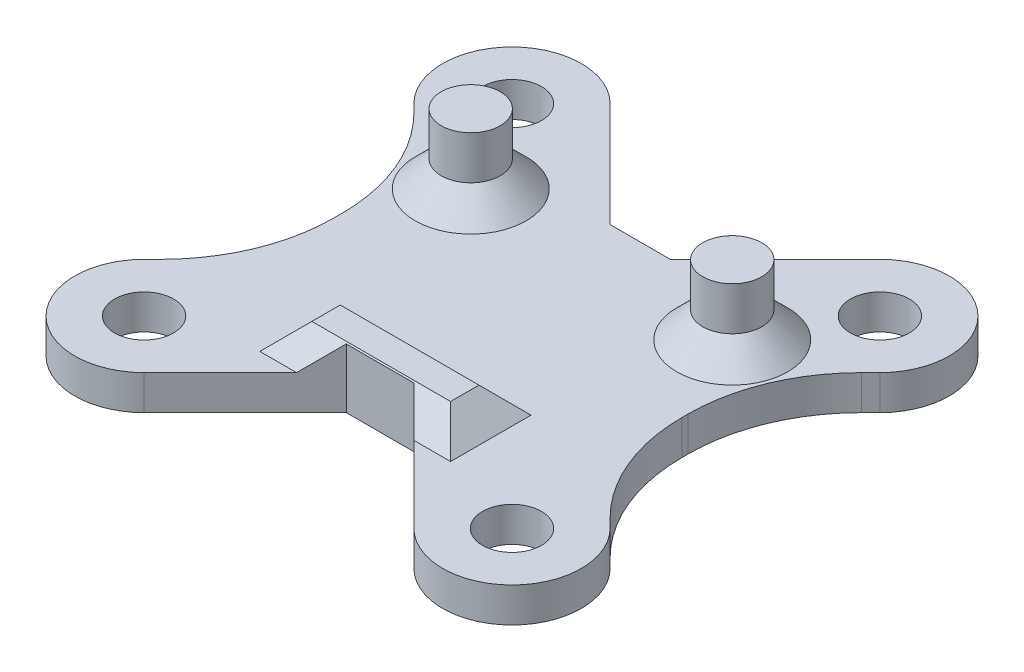
SolidWorks part; units mm, degrees
ref_plane "Front Plane" through (0, 0, 0) normal (0, 0, 1) x (1, 0, 0)
ref_plane "Top Plane" through (0, 0, 0) normal (0, 1, 0) x (1, 0, 0)
ref_plane "Right Plane" through (0, 0, 0) normal (1, 0, 0) x (0, 0, -1)
sketch "Sketch2" plane through (0, 0, 0) normal (0, 1, 0) x (1, 0, 0)
  line L0 (-10.6066, 10.6066) -> (10.6066, -10.6066) construction
  line L1 (-10.6066, -10.6066) -> (10.6066, 10.6066) construction
  line L2 (-13.435, 7.7782) -> (-10.0286, 4.3718)
  line L3 (9.9714, -4.3145) -> (9.9714, 4.3145)
  line L4 (-7.7782, -13.435) -> (-1.9497, -7.6066)
  line L5 (-7.7782, 13.435) -> (-1.7365, 7.3934)
  line L6 (-13.435, -7.7782) -> (-10.0286, -4.3718)
  line L7 (1.7365, 7.3934) -> (7.7782, 13.435)
  line L8 (1.9497, -7.6066) -> (7.7782, -13.435)
  line L9 (1.7365, 7.3934) -> (-1.7365, 7.3934)
  line L10 (9.9714, 4.3145) -> (13.435, 7.7782)
  line L11 (9.9714, -4.3145) -> (13.435, -7.7782)
  line L12 (1.9497, -7.6066) -> (-1.9497, -7.6066)
  line L13 (-10.0286, -4.3718) -> (-10.0286, 4.3718)
  circle A0 centre (-10.6066, -10.6066) radius 1.7
  circle A1 centre (10.6066, -10.6066) radius 1.7
  circle A2 centre (10.6066, 10.6066) radius 1.7
  circle A3 centre (-10.6066, 10.6066) radius 1.7
  arc A4 (-7.7782, 13.435) -> (-13.435, 7.7782) centre (-10.6066, 10.6066) ccw
  arc A5 (13.435, 7.7782) -> (7.7782, 13.435) centre (10.6066, 10.6066) ccw
  arc A6 (7.7782, -13.435) -> (13.435, -7.7782) centre (10.6066, -10.6066) ccw
  arc A7 (-13.435, -7.7782) -> (-7.7782, -13.435) centre (-10.6066, -10.6066) ccw
  point P24 (0, 0)
extrude "Boss-Extrude1" add sketch "Sketch2" along normal blind 2 contours L9 L5 A4 L2 L13 L6 A7 L4 L12 L8 A6 L11 L3 L10 A5 L7
sketch "Sketch3" plane through (0, 2, 0) normal (0, 1, 0) x (1, 0, 0)
  point P0 (-10.6066, -10.6066)
  point P2 (10.6066, -10.6066)
  point P4 (10.6066, 10.6066)
  point P6 (-10.6066, 10.6066)
hole_wizard "M3 Clearance Hole1" positions "Sketch3" profile "Sketch4" hole size "M3" standard "ISO" end condition through all
sketch "Sketch4" plane through (-10.6066, 2, 10.6066) normal (1, 0, 0) x (0, 0, 1)
  line L0 (0, 0) -> (0, 2)
  line L1 (0, 2) -> (1.7, 2)
  line L2 (1.7, 2) -> (1.7, 0)
  line L5 (1.7, 0) -> (0, 0)
  line L11 (0, -6.35) -> (0, 107.95) construction
  dimension "Thru Hole Dia." = 3.4
  dimension "Thru Hole Depth" = 2
sketch "Sketch5" plane through (0, 2, 0) normal (0, 1, 0) x (1, 0, 0)
  line L0 (-7.54, 5.16) -> (7.54, 5.16) construction
  line L1 (-10.32, -7.54) -> (10.32, -7.54)
  line L2 (-10.32, -7.54) -> (-10.32, 7.54)
  line L3 (-10.32, 7.54) -> (10.32, 7.54)
  line L4 (10.32, -7.54) -> (10.32, 7.54)
  line L5 (-10.32, -7.54) -> (10.32, 7.54)
  line L6 (10.32, -7.54) -> (-10.32, 7.54)
  line L7 (0, -7.54) -> (4, -7.54)
  line L9 (0, -7.54) -> (-4, -7.54)
  line L12 (-4, -7.54) -> (4, -7.54)
  line L13 (-4, -7.54) -> (-4, -5.9041)
  line L14 (-4, -5.9041) -> (4, -5.9041)
  line L15 (4, -7.54) -> (4, -5.9041)
  circle A0 centre (-7.54, 5.16) radius 1.7
  circle A1 centre (7.54, 5.16) radius 1.7
  point P4 (-7.54, 5.16)
  point P5 (7.54, 5.16)
  point P14 (-7.54, 5.16)
  point P16 (7.54, 5.16)
  dimension "D7" = 3.4
  dimension "D8" = 3.4
  dimension "D1" = 20.64
  dimension "D2" = 15.08
  dimension "D3" = 2.78
  dimension "D4" = 2.38
  dimension "D5" = 2.78
  dimension "D6" = 2.38
  dimension "D9" = 4
  dimension "D10" = 4
extrude "Boss-Extrude2" add sketch "Sketch5" along normal blind 4 contours L5 A1 | A1 L0 L5 | L0 A1 L5 | A0 region at (7.1394, 2, -6.0202) region at (6.2883, 2, -4.8997) region at (7.8774, 2, -4.6982)
fillet "Fillet1" radius 10 4 edges at (9.9714, 1, -4.3145) (9.9714, 1, 4.3145) (-10.0286, 1, 4.3718) (-10.0286, 1, -4.3718)
extrude "Boss-Extrude3" add sketch "Sketch5<3>" along normal blind 1.5 contours L1 L15 L14 L13 region at (0, 2, 6.722)
sketch "Sketch5<3>" plane through (0, 2, 0) normal (0, 1, 0) x (1, 0, 0) same geometry as "Sketch5"
chamfer "Chamfer1" distance 1.5 angle 45 2 edges at (7.54, 2, -3.46) (-7.54, 2, -3.46)
chamfer "Chamfer2" distance 1.5 angle 45 4 edges at (0, 2, 5.9041) (-4, 2, 6.722) (0, 2, 7.54) (4, 2, 6.722)
